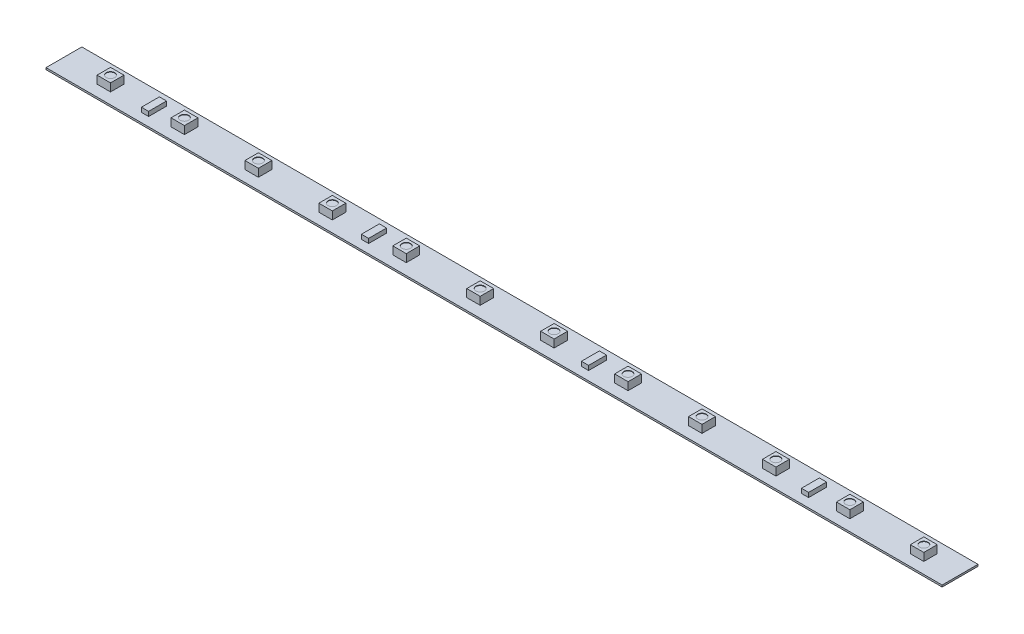
SolidWorks part; units mm, degrees
ref_plane "Front" through (0, 0, 0) normal (0, 0, 1) x (1, 0, 0)
ref_plane "Top" through (0, 0, 0) normal (0, 1, 0) x (1, 0, 0)
ref_plane "Right" through (0, 0, 0) normal (1, 0, 0) x (0, 0, -1)
sketch "Sketch1" plane through (0, 0, 0) normal (0, 1, 0) x (1, 0, 0)
  line L0 (0, 0) -> (0, -4) construction
  line L1 (-100, 4) -> (100, 4)
  line L2 (-100, 4) -> (-100, -4)
  line L3 (-100, -4) -> (100, -4)
  line L4 (100, 4) -> (100, -4)
  line L5 (0, -50) -> (0, 50) construction
  line L6 (0, 0) -> (100, 0) construction
  line L7 (-50, 0) -> (50, 0) construction
  dimension "D1" = 8
  dimension "D2" = 200
extrude "Boss-Extrude1" add sketch "Sketch1" along normal blind 0.4
sketch "Sketch2" plane through (0, 0.4, 0) normal (0, 1, 0) x (1, 0, 0)
  line L0 (80.2754, 0) -> (93.4, 0) construction
  line L1 (90.4, 1.5) -> (93.4, 1.5)
  line L2 (90.4, 1.5) -> (90.4, -1.5)
  line L3 (90.4, -1.5) -> (93.4, -1.5)
  line L4 (93.4, 1.5) -> (93.4, -1.5)
  line L5 (-50, 0) -> (50, 0) construction
  line L6 (100, -4) -> (100, 4) construction
  dimension "D1" = 3
  dimension "D2" = 6.6
extrude "Boss-Extrude2" add sketch "Sketch2" along normal blind 1.75
sketch "Sketch3" plane through (0, 2.15, 0) normal (0, 1, 0) x (1, 0, 0)
  line L0 (91.9, 1.5) -> (91.9, -1.5) construction
  line L1 (93.4, 1.5) -> (90.4, 1.5) construction
  line L2 (90.4, -1.5) -> (93.4, -1.5) construction
  line L3 (90.4, 0) -> (93.4, 0) construction
  line L4 (90.4, 1.5) -> (90.4, -1.5) construction
  line L5 (93.4, -1.5) -> (93.4, 1.5) construction
  circle A0 centre (91.9, 0) radius 0.95
  dimension "D1" = 1.9
extrude "Cut-Extrude1" cut sketch "Sketch3" against normal blind 0.1
pattern_linear "LPattern1" count 12 spacing 16.5 along (-1, 0, 0) of "Cut-Extrude1", "Boss-Extrude2"
sketch "Sketch4" plane through (0, 0.4, 0) normal (0, 1, 0) x (1, 0, 0)
  line L0 (75.4, 0) -> (100, 0) construction
  line L1 (66.6, 2) -> (68.2, 2)
  line L2 (66.6, 2) -> (66.6, -2)
  line L3 (66.6, -2) -> (68.2, -2)
  line L4 (68.2, 2) -> (68.2, -2)
  line L5 (100, -4) -> (100, 4) construction
  line L6 (67.4, 2) -> (67.4, -2) construction
  dimension "D1" = 4
  dimension "D2" = 1.6
  dimension "D3" = 8
extrude "Boss-Extrude3" add sketch "Sketch4" along normal blind 1
pattern_linear "LPattern2" count 4 spacing 49.1 along (-1, 0, 0) of "Boss-Extrude3"
sketch "Sketch5" plane through (-100, 0, 0) normal (-1, 0, 0) x (0, 0, 1)
  line L0 (0, 2.15) -> (0, 0) construction
  line L1 (-1.5, 2.15) -> (1.5, 2.15) construction
  line L2 (-1.825, 1.3) -> (-1.825, 0.4) construction
  line L3 (1.825, 1.3) -> (1.825, 0.4) construction
  line L4 (-4, 0.4) -> (4, 0.4) construction
  line L5 (0.925, 2.2) -> (1.7564, 2.2) construction
  circle A0 centre (-0.925, 1.3) radius 0.9
  circle A1 centre (0.925, 1.3) radius 0.9
  dimension "D2" = 3.65
  dimension "D1" = 1.8
extrude "Boss-Extrude4" [suppressed] add sketch "Sketch5" along normal blind 1000 from offset 2 separate body offset against normal yes
sketch "Sketch6" [suppressed] plane through (-1098, 0, 0) normal (-1, 0, 0) x (0, 0, 1)
  line L1 (-2.81, 3.88) -> (2.81, 3.88)
  line L2 (-2.81, 3.88) -> (-2.81, -1.28)
  line L3 (-2.81, -1.28) -> (2.81, -1.28)
  line L4 (2.81, 3.88) -> (2.81, -1.28)
  line L5 (0, 0) -> (0, 3.88) construction
  line L6 (0, -50) -> (0, 50) construction
  line L7 (-0.925, 1.3) -> (0.925, 1.3) construction
  dimension "D1" = 5.62
  dimension "D2" = 5.16
extrude "Boss-Extrude5" [suppressed] add sketch "Sketch6" along normal blind 12.8
sketch "Sketch7" [suppressed] plane through (0, 3.88, 0) normal (0, 1, 0) x (1, 0, 0)
  line L0 (-1110.8, 0) -> (-1098, 0) construction
  line L1 (-1110.8, 2.81) -> (-1102.87, 2.81)
  line L2 (-1110.8, 2.81) -> (-1110.8, 1.59)
  line L3 (-1110.8, 1.59) -> (-1102.87, 1.59)
  line L4 (-1102.87, 2.81) -> (-1102.87, 1.59)
  line L5 (-1110.8, -2.81) -> (-1110.8, 2.81) construction
  line L6 (-1098, -2.81) -> (-1098, 2.81) construction
  line L7 (-1102.87, -2.81) -> (-1102.87, -1.59)
  line L8 (-1110.8, -1.59) -> (-1102.87, -1.59)
  line L9 (-1110.8, -2.81) -> (-1110.8, -1.59)
  line L10 (-1110.8, -2.81) -> (-1102.87, -2.81)
  dimension "D1" = 7.93
  dimension "D2" = 1.22
extrude "Boss-Extrude6" [suppressed] add sketch "Sketch7" along normal blind 1.3
